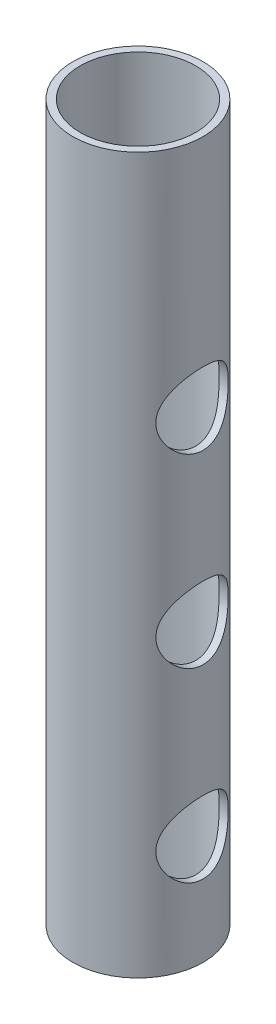
SolidWorks part; units mm, degrees
material "PTFE (general)"
ref_plane "Front Plane" through (0, 0, 0) normal (0, 0, 1) x (1, 0, 0)
ref_plane "Top Plane" through (0, 0, 0) normal (0, 1, 0) x (1, 0, 0)
ref_plane "Right Plane" through (0, 0, 0) normal (1, 0, 0) x (0, 0, -1)
sketch "Sketch1" plane through (0, 0, 0) normal (0, 1, 0) x (1, 0, 0)
  circle A0 centre (0, 0) radius 17.875
  circle A1 centre (0, 0) radius 15.875
  dimension "D1" = 2
  dimension "D2" = 31.75
extrude "Boss-Extrude1" add sketch "Sketch1" along normal blind 196.5
sketch "Sketch2" plane through (0, 0, 0) normal (1, 0, 0) x (0, 0, -1)
  line L0 (15.875, 196.5) -> (-15.875, 196.5) construction
  circle A0 centre (0, 131.8) radius 9.94
  circle A1 centre (0, 80.8) radius 9.94
  circle A2 centre (0, 29.8) radius 9.94
  dimension "D2" = 19.88
  dimension "D3" = 19.88
  dimension "D4" = 19.88
  dimension "D1" = 64.7
  dimension "D5" = 51
  dimension "D6" = 51
extrude "Cut-Extrude1" cut sketch "Sketch2" along normal through all
